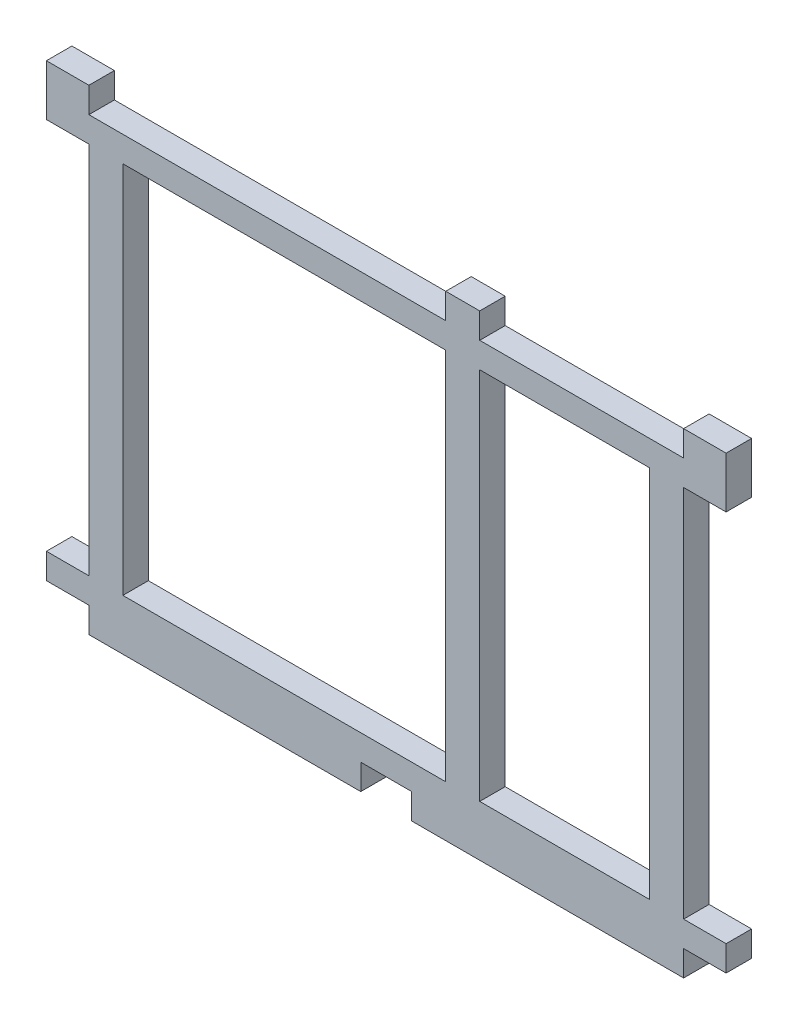
SolidWorks part; units mm, degrees
material "Custom Plastic"
ref_plane "Front Plane" through (0, 0, 0) normal (0, 0, 1) x (1, 0, 0)
ref_plane "Top Plane" through (0, 0, 0) normal (0, 1, 0) x (1, 0, 0)
ref_plane "Right Plane" through (0, 0, 0) normal (1, 0, 0) x (0, 0, -1)
sketch "Sketch1" plane through (0, 0, 0) normal (0, 0, 1) x (1, 0, 0)
  line L0 (-41.2824, 37.1909) -> (-36.2824, 37.1909)
  line L1 (-36.2824, 37.1909) -> (-36.2824, -6.8091)
  line L2 (-36.2824, -6.8091) -> (-41.2824, -6.8091)
  line L3 (-41.2824, -6.8091) -> (-41.2824, -9.8091)
  line L4 (-41.2824, -9.8091) -> (-36.2824, -9.8091)
  line L5 (-36.2824, -9.8091) -> (-36.2824, -12.8091)
  line L6 (-36.2824, -12.8091) -> (-4.2824, -12.8091)
  line L7 (-4.2824, -12.8091) -> (-4.2824, -9.8091)
  line L8 (-4.2824, -9.8091) -> (1.7176, -9.8091)
  line L9 (1.7176, -9.8091) -> (1.7176, -12.8091)
  line L10 (1.7176, -12.8091) -> (33.7176, -12.8091)
  line L11 (33.7176, -12.8091) -> (33.7176, -9.8091)
  line L12 (33.7176, -9.8091) -> (38.7176, -9.8091)
  line L13 (38.7176, -9.8091) -> (38.7176, -6.8091)
  line L14 (38.7176, -6.8091) -> (33.7176, -6.8091)
  line L15 (33.7176, -6.8091) -> (33.7176, 37.1909)
  line L16 (33.7176, 37.1909) -> (38.7176, 37.1909)
  line L17 (38.7176, 37.1909) -> (38.7176, 43.1909)
  line L27 (-41.2824, 43.1909) -> (-41.2824, 37.1909)
  line L28 (-36.2824, -6.8091) -> (33.7176, -6.8091) construction
  line L29 (-36.2824, 37.1909) -> (33.7176, 37.1909) construction
  line L30 (-32.2824, -6.8091) -> (-32.2824, 37.1909)
  line L31 (-32.2824, 37.1909) -> (5.7176, 37.1909)
  line L32 (5.7176, 37.1909) -> (5.7176, -6.8091)
  line L33 (5.7176, -6.8091) -> (-32.2824, -6.8091)
  line L34 (9.7176, -6.8091) -> (9.7176, 37.1909)
  line L35 (9.7176, 37.1909) -> (29.7176, 37.1909)
  line L36 (29.7176, 37.1909) -> (29.7176, -6.8091)
  line L37 (29.7176, -6.8091) -> (9.7176, -6.8091)
  line L38 (38.7176, 43.1909) -> (33.7176, 43.1909)
  line L39 (33.7176, 43.1909) -> (33.7176, 40.1909)
  line L40 (33.7176, 40.1909) -> (9.7176, 40.1909)
  line L41 (9.7176, 40.1909) -> (9.7176, 43.1909)
  line L42 (9.7176, 43.1909) -> (5.7176, 43.1909)
  line L43 (5.7176, 43.1909) -> (5.7176, 40.1909)
  line L44 (5.7176, 40.1909) -> (-36.2824, 40.1909)
  line L45 (-36.2824, 40.1909) -> (-36.2824, 43.1909)
  line L46 (-36.2824, 43.1909) -> (-41.2824, 43.1909)
  point P21 (0, 0)
  point P28 (0, 0)
  point P39 (0, 0)
  point P40 (0, 0)
  point P41 (0, 0)
  point P42 (-41.2937, 40.2876)
  point P43 (0, 0)
  point P44 (-41.2824, 43.4445)
  point P45 (38.7176, 43.2487)
  dimension "D2" = 3
  dimension "D3" = 3
  dimension "D4" = 80
  dimension "D5" = 4
  dimension "D6" = 6
  dimension "D7" = 5
  dimension "D8" = 4
  dimension "D9" = 4
  dimension "D10" = 20
  dimension "D11" = 6
  dimension "D12" = 3
extrude "Boss-Extrude1" add sketch "Sketch1" along normal blind 3
